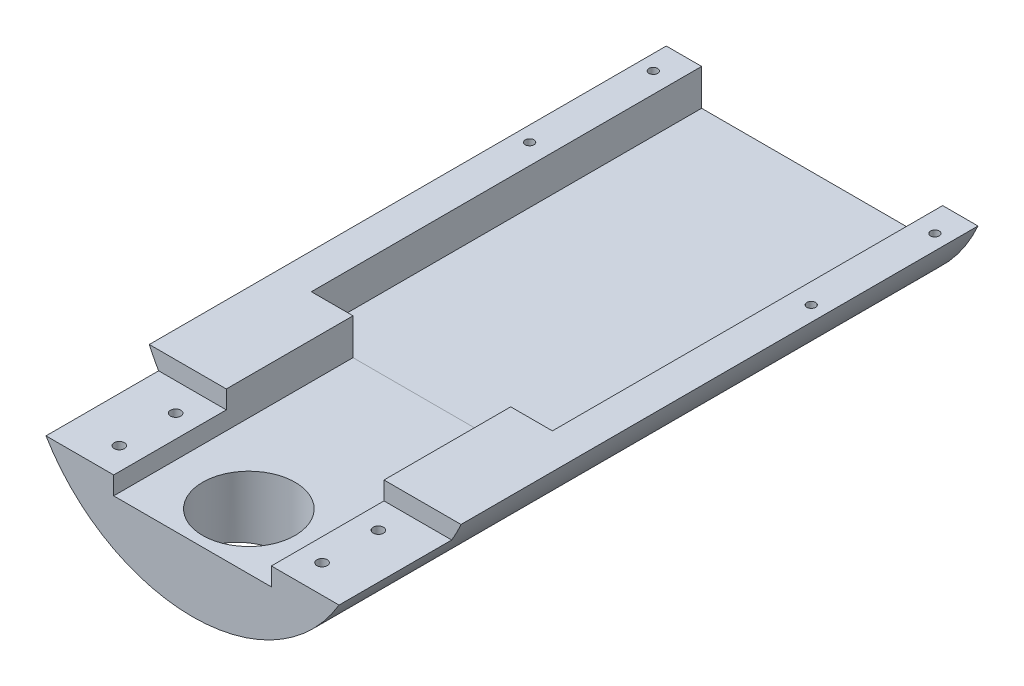
SolidWorks part; units mm, degrees
material "eSUN PLA+ (Not accurate)"
ref_plane "Front Plane" through (0, 0, 0) normal (0, 0, 1) x (1, 0, 0)
ref_plane "Top Plane" through (0, 0, 0) normal (0, 1, 0) x (1, 0, 0)
ref_plane "Right Plane" through (0, 0, 0) normal (1, 0, 0) x (0, 0, -1)
sketch "Sketch1" plane through (0, 0, 0) normal (0, 0, 1) x (1, 0, 0)
  line L0 (-69.1908, -30.525) -> (-35, -30.525)
  line L1 (-35, -30.525) -> (-35, -46.625)
  line L2 (-35, -46.625) -> (35, -46.625)
  line L3 (35, -46.625) -> (35, -30.525)
  line L4 (35, -30.525) -> (69.1908, -30.525)
  circle A0 centre (0, 0) radius 75.625 construction
  arc A1 (-69.1908, -30.525) -> (69.1908, -30.525) centre (0, 0) ccw
  point P10 (0, -75.625)
  dimension "D1" = 151.25
  dimension "D2" = 70
  dimension "D3" = 29
  dimension "D4" = 16.1
extrude "Boss-Extrude1" add sketch "Sketch1" along normal blind 279.5 from offset 15
sketch "Sketch2" plane through (0, 0, 294.5) normal (0, 0, 1) x (1, 0, 0)
  line L0 (-35, -30.525) -> (-35, -38.575) construction
  line L1 (-35, -46.625) -> (-35, -30.525) construction
  line L2 (-35, -38.575) -> (-35, -46.625) construction
  line L3 (-35, -30.525) -> (-35, -38.575)
  line L6 (-35, -38.575) -> (-65.047, -38.575)
  line L8 (-69.1908, -30.525) -> (-35, -30.525)
  arc A0 (-69.1908, -30.525) -> (-65.047, -38.575) centre (0, 0) ccw
  arc A2 (-69.1908, -30.525) -> (69.1908, -30.525) centre (0, 0) ccw construction
sketch "Sketch3" plane through (0, 0, 15) normal (0, 0, -1) x (-1, 0, 0)
  line L0 (-35, -46.625) -> (35, -46.625) construction
  line L1 (53.5, 46.625) -> (-53.5, 46.625)
  line L2 (53.5, 46.625) -> (53.5, -46.625)
  line L3 (53.5, -46.625) -> (-53.5, -46.625)
  line L4 (-53.5, 46.625) -> (-53.5, -46.625)
  line L5 (53.5, 46.625) -> (-53.5, -46.625) construction
  line L6 (53.5, -46.625) -> (-53.5, 46.625) construction
  point P0 (0, 0)
  dimension "D1" = 107
extrude "Cut-Extrude1" cut sketch "Sketch3" against normal blind 173.25
sketch "Sketch4" plane through (0, -46.625, 0) normal (0, 1, 0) x (1, 0, 0)
  line L1 (0, -15) -> (0, -294.5) construction
  line L2 (53.5, -15) -> (-53.5, -15) construction
  line L3 (35, -294.5) -> (-35, -294.5) construction
  circle A0 centre (0, -269.5) radius 20.5
  dimension "D1" = 41
  dimension "D2" = 25
extrude "Cut-Extrude2" cut sketch "Sketch4" against normal through all
extrude "Cut-Extrude3" cut sketch "Sketch2" against normal blind 50
sketch "Sketch6" plane through (0, 0, 294.5) normal (0, 0, 1) x (1, 0, 0)
  line L0 (-42.2865, -46.625) -> (-59.542, -46.625)
  line L1 (-59.542, -46.625) -> (-42.2865, -46.625)
  line L2 (-42.2865, -46.625) -> (-42.2865, -62.6976)
  arc A0 (-59.542, -46.625) -> (-42.2865, -62.6976) centre (0, 0) ccw
  arc A1 (-65.047, -38.575) -> (69.1908, -30.525) centre (0, 0) ccw construction
mirror "Mirror1" about plane through (0, 0, 0) normal (1, 0, 0) of "Cut-Extrude3"
sketch "Sketch7" plane through (0, -38.575, 0) normal (0, 1, 0) x (1, 0, 0)
  line L1 (35, -269.5) -> (65.047, -269.5) construction
  line L4 (35, -294.5) -> (65.047, -294.5)
  line L5 (65.047, -294.5) -> (65.047, -244.5)
  line L6 (65.047, -244.5) -> (35, -244.5)
  line L7 (35, -244.5) -> (35, -294.5)
  line L8 (35, -294.5) -> (65.047, -294.5) construction
  line L9 (65.047, -294.5) -> (65.047, -244.5) construction
  line L10 (65.047, -244.5) -> (35, -244.5) construction
  line L11 (35, -244.5) -> (35, -294.5) construction
  circle A0 centre (45, -257) radius 2.3
  circle A1 centre (45, -282) radius 2.3
  dimension "D2" = 4.6
  dimension "D3" = 25
  dimension "D4" = 10
  dimension "D1" = 0
extrude "Cut-Extrude5" cut sketch "Sketch7" against normal through all
mirror "Mirror2" about plane through (0, 0, 0) normal (1, 0, 0) of "Cut-Extrude5"
ref_plane "Plane1" through (0, -52.075, 0) normal (0, 1, 0) x (1, 0, 0)
sketch "Sketch11" plane through (0, -52.075, 0) normal (0, 1, 0) x (1, 0, 0)
  circle A0 centre (45, -257) radius 2.3 construction
  circle A1 centre (45, -282) radius 2.3 construction
  circle A2 centre (45, -257) radius 2.3 construction
  circle A3 centre (45, -282) radius 2.3 construction
  circle A4 centre (45, -282) radius 3.8
  circle A5 centre (45, -257) radius 3.8
  dimension "D1" = 7.6
ref_plane "Plane2" through (0, 0, 154.5) normal (0, 0, 1) x (1, 0, 0)
other "Intersect1" [suppressed]
move or copy body "Body-Convert to Mesh Body2" [suppressed] bodies to move or copy 114 copy no translate (0, 0, 0)
sketch "Sketch13" plane through (0, -46.625, 0) normal (0, 1, 0) x (1, 0, 0)
  line L0 (35, -188.25) -> (-35, -188.25)
  line L1 (-35, -294.5) -> (-35, -188.25) construction
  line L2 (-35, -188.25) -> (-53.5, -188.25) construction
split line "Split Line1"
extrude "Cut-Extrude8" cut sketch "Sketch11" along normal blind 7 and the other way through all
mirror "Mirror3" about plane through (0, 0, 0) normal (1, 0, 0) of "Cut-Extrude8"
sketch "Sketch14" plane through (0, -30.525, 0) normal (0, 1, 0) x (1, 0, 0)
  circle A0 centre (62.5, -82.35) radius 1.875 construction
  circle A1 centre (62.5, -27.45) radius 1.875 construction
  circle A2 centre (62.5, -82.35) radius 1.875 construction
  circle A3 centre (62.5, -27.45) radius 1.875 construction
  circle A5 centre (62.5, -27.45) radius 1.93
  circle A6 centre (62.5, -82.35) radius 1.93
  dimension "D1" = 3.86
extrude "Cut-Extrude9" cut sketch "Sketch14" against normal blind 7.25
mirror "Mirror4" about plane through (0, 0, 0) normal (1, 0, 0) of "Cut-Extrude9"
ref_plane "Plane3" through (0, 0, 87) normal (0, 0, 1) x (1, 0, 0)
other "Intersect2" [suppressed]
move or copy body "Body-Convert to Mesh Body3" [suppressed] bodies to move or copy 122 copy no translate (0, 0, 0) parameters "D1"=0, "D2"=0, "D3"=0
sketch "Sketch18" plane through (0, 0, 15) normal (0, 0, -1) x (-1, 0, 0)
  line L0 (0, -56.625) -> (0, -46.625)
  line L1 (0, -75.625) -> (0, -56.625) construction
  line L4 (-53.5, -46.625) -> (53.5, -46.625) construction
  line L13 (42.2078, -56.625) -> (-42.2078, -56.625)
  line L14 (42.2078, -56.625) -> (-42.2078, -56.625)
  line L17 (-44.3364, -50.125) -> (44.3364, -50.125)
  line L19 (44.3364, -56.125) -> (-44.3364, -56.125)
  line L20 (-44.3364, -56.125) -> (-44.3364, -50.125)
  line L21 (44.3364, -56.125) -> (44.3364, -50.125)
  line L27 (28.4868, -64.625) -> (-28.4868, -64.625) construction
  line L28 (30.1174, -64.625) -> (-30.1174, -64.625)
  arc A0 (-44.3364, -56.125) -> (44.3364, -56.125) centre (0, 1.8987) ccw
  arc A12 (-42.2078, -56.625) -> (42.2078, -56.625) centre (0, 0) ccw
  arc A15 (-42.2078, -56.625) -> (42.2078, -56.625) centre (0, 0) ccw
  arc A26 (-69.1908, -30.525) -> (69.1908, -30.525) centre (0, 0) ccw construction
  point P3 (0, -71.125)
  point P4 (0, -70.625)
  dimension "D6" = 0.5
  dimension "D7" = 1.8987
  dimension "D8" = 0.5
  dimension "D9" = 6
  dimension "D3" = 0
extrude "Cut-Extrude10" cut sketch "Sketch18" against normal blind 125.5 contours L20 L19 L0 L17 | L19 L21 L17 L0 | L1 L28 A15 L14 | L28 L1 L14 A15 | A15 L28 A0 L19 L0 L14 | A15 L14 L0 L19 A0 L28 region at (21.1039, -56.1736, 15) region at (-18.1851, -60.373, 15) region at (-0.4514, -56.375, 15) region at (18.1851, -60.373, 15) region at (22.1682, -53.125, 15) region at (-22.1682, -53.125, 15)
ref_plane "Plane4" through (0, 0, 40) normal (0, 0, -1) x (-1, 0, 0)
sketch "Sketch19" plane through (0, 0, 40) normal (0, 0, -1) x (-1, 0, 0)
  line L0 (30.1174, -64.625) -> (-30.1174, -64.625) construction
  line L1 (30.1174, -64.625) -> (-30.1174, -64.625)
  arc A0 (-44.3364, -56.125) -> (44.3364, -56.125) centre (0, 1.8987) ccw construction
  arc A1 (-44.3364, -56.125) -> (44.3364, -56.125) centre (0, 1.8987) ccw
extrude "Cut-Extrude12" cut sketch "Sketch19" against normal blind 100.5 contours L1 A1 region at (0, -67.2352, 40)
ref_plane "Plane5" through (0, 0, 65) normal (0, 0, -1) x (-1, 0, 0)
sketch "Sketch20" plane through (0, 0, 65) normal (0, 0, -1) x (-1, 0, 0)
  line L0 (-44.3364, -56.125) -> (-44.3364, -50.125) construction
  line L1 (44.3364, -56.125) -> (-44.3364, -56.125) construction
  line L2 (44.3364, -56.125) -> (44.3364, -50.125) construction
  line L3 (-44.3364, -50.125) -> (44.3364, -50.125) construction
  line L4 (-44.3364, -56.125) -> (-44.3364, -50.125)
  line L5 (44.3364, -56.125) -> (-44.3364, -56.125)
  line L6 (44.3364, -56.125) -> (44.3364, -50.125)
  line L7 (-44.3364, -50.125) -> (44.3364, -50.125)
extrude "Boss-Extrude2" add sketch "Sketch20" against normal up to surface (75.5 mm away) up to face at (0, -56.875, 140.5)
sketch "screw head hole" plane through (0, 0, 15) normal (0, 0, -1) x (-1, 0, 0)
  circle A0 centre (0, -68.825) radius 1.45 construction
  circle A1 centre (0, -68.825) radius 1.45
  circle A2 centre (0, -68.825) radius 3.3
  dimension "D1" = 6.6
extrude "Cut-Extrude13" cut sketch "screw head hole" against normal blind 7 contours A1 | A2 A1 region at (0, -68.825, 15) region at (3.2067, -68.825, 15)
ref_plane "Plane6" [suppressed] through (0, 0, 149.5) normal (0, 0, 1) x (1, 0, 0)
split "Split1" [suppressed] bodies to split 130
equation "\"4mmmm\"= 3.85"
equation "\"8mmmm\"=6.4"
equation "\"D1@Boss-Extrude3@Connection Idea<1>.Part\" = \"totExtrusion@Connection Idea<1>.Part\""
equation "\"D1@Cut-Extrude10\" = \"totExtrusion@Connection Idea<1>.Part\" + \"extraSpaceForBigExt\""
equation "\"lockHolder\"= 25mm"
equation "\"D1@Cut-Extrude12\" = \"totExtrusion@Connection Idea<1>.Part\" + \"extraSpaceForBigExt\" - \"lockHolder\""
equation "\"extraSpaceForBigExt\"= 0.5mm"
equation "\"D8@Sketch18\"=\"D6@Sketch18\""
